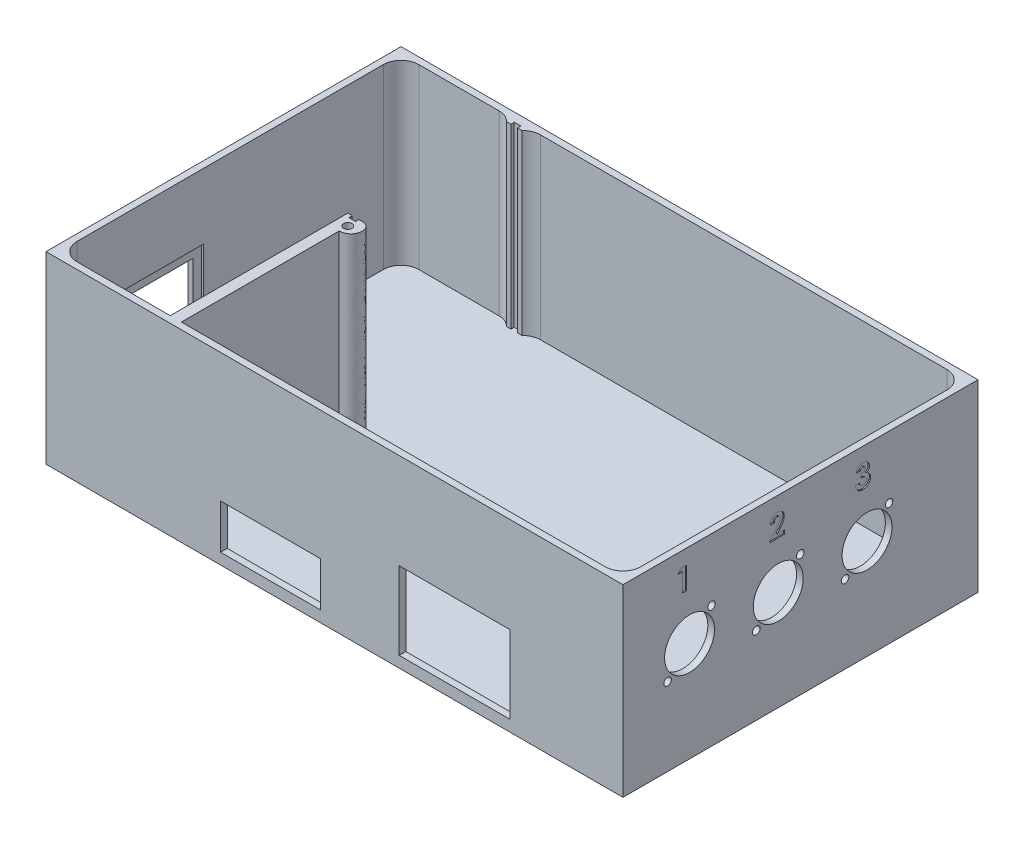
SolidWorks part; units mm, degrees
ref_plane "Ebene vorne" through (0, 0, 0) normal (0, 0, 1) x (1, 0, 0)
ref_plane "Ebene oben" through (0, 0, 0) normal (0, 1, 0) x (1, 0, 0)
ref_plane "Ebene rechts" through (0, 0, 0) normal (1, 0, 0) x (0, 0, -1)
sketch "Sketch1" plane through (0, 0, 0) normal (0, 1, 0) x (1, 0, 0)
  line L1 (-130, -80) -> (130, -80)
  line L2 (-130, -80) -> (-130, 80)
  line L3 (-130, 80) -> (130, 80)
  line L4 (130, -80) -> (130, 80)
  line L5 (-130, -80) -> (130, 80) construction
  line L6 (-130, 80) -> (130, -80) construction
  point P0 (0, 0)
  dimension "D1" = 260
  dimension "D2" = 160
extrude "Boss-Extrude1" add sketch "Sketch1" against normal blind 3
sketch "Sketch2" plane through (0, 0, 0) normal (0, 1, 0) x (1, 0, 0)
  line L4 (130, -80) -> (130, 80)
  line L5 (130, 80) -> (-130, 80)
  line L6 (-130, 80) -> (-130, -80)
  line L7 (-130, -80) -> (130, -80)
  line L8 (130, -80) -> (130, 80)
  line L9 (130, 80) -> (-130, 80)
  line L10 (-130, 80) -> (-130, -80)
  line L11 (-130, -80) -> (130, -80)
  dimension "D1" = 0
extrude "Extrude-Thin2" add sketch "Sketch2" along normal blind 80 thin thin type one direction reverse wall 3
fillet "Fillet1" radius 8 4 edges at (127, 40, 77) (127, 40, -77) (-127, 40, 77) (-127, 40, -77)
sketch "Sketch3" plane through (0, 0, 0) normal (0, 1, 0) x (1, 0, 0)
  line L0 (-119, -77) -> (119, -77) construction
  line L1 (-77, -77) -> (-72, -77)
  line L2 (-77, -77) -> (-77, 3)
  line L4 (-72, -77) -> (-72, -5.9012)
  line L5 (-127, 69) -> (-127, -69) construction
  line L8 (-77, 3) -> (-75, 3)
  line L9 (-75, 3) -> (-75, 1.5)
  line L10 (-75, 1.5) -> (-72, 1.5)
  line L11 (-72, 1.5) -> (-72, 3)
  line L12 (-72, 3) -> (-70, 3)
  spline S0 degree 3 poles (-72, -5.9012) (-65.4058, -5.4857) (-65.3292, 2.681) (-70, 3) knots 0 0 0 0 1 1 1 1
  dimension "D1" = 50
  dimension "D2" = 2
  dimension "D3" = 80
  dimension "D5" = 3
  dimension "D6" = 2
  dimension "D9" = 5
  dimension "D10" = 1.5
extrude "Boss-Extrude2" add sketch "Sketch3" along normal up to surface (80 mm away) up to face at (0, 80, 0)
sketch "Sketch4" plane through (0, 0, 0) normal (0, 1, 0) x (1, 0, 0)
  line L0 (-73.5, 1.5) -> (-73.5, 77) construction
  line L1 (-73.5, 39.25) -> (-68.4781, 39.25) construction
  line L2 (-70, 77) -> (-70, 74.5)
  line L3 (-70, 74.5) -> (-72, 74.5)
  line L4 (-72, 74.5) -> (-72, 76)
  line L5 (-72, 76) -> (-75, 76)
  line L6 (-75, 76) -> (-75, 74.5)
  line L7 (-75, 74.5) -> (-77, 74.5)
  line L8 (-77, 74.5) -> (-77, 77)
  line L9 (-70, 77) -> (-77, 77)
  line L10 (-72, 1.5) -> (-75, 1.5) construction
  line L11 (119, 77) -> (-119, 77) construction
  point P12 (-73.5, 76)
  dimension "D1" = 1.5
  dimension "D2" = 2.5
  dimension "D3" = 2
extrude "Boss-Extrude3" add sketch "Sketch4" along normal up to surface (80 mm away) up to face at (0, 80, 0)
fillet "Fillet2" radius 8 2 edges at (-77, 40, -77) (-70, 40, -77)
sketch "Sketch5" plane through (-130, 0, 0) normal (-1, 0, 0) x (0, 0, 1)
  line L0 (-80, -3) -> (80, -3) construction
  line L1 (63.95, 17.55) -> (16.05, 17.55)
  line L2 (63.95, 17.55) -> (63.95, 46.45)
  line L3 (63.95, 46.45) -> (16.05, 46.45)
  line L4 (16.05, 17.55) -> (16.05, 46.45)
  line L5 (63.95, 17.55) -> (16.05, 46.45) construction
  line L6 (63.95, 46.45) -> (16.05, 17.55) construction
  line L7 (80, -3) -> (80, 80) construction
  point P0 (40, 32)
  dimension "D1" = 28.9
  dimension "D2" = 47.9
  dimension "D3" = 35
  dimension "D4" = 40
extrude "Cut-Extrude1" cut sketch "Sketch5" against normal up to next
sketch "Sketch6" plane through (-127, 0, 0) normal (-1, 0, 0) x (0, 0, 1)
  line L0 (12.05, 13.55) -> (67.95, 13.55)
  line L1 (67.95, 13.55) -> (67.95, 50.45)
  line L2 (67.95, 50.45) -> (12.05, 50.45)
  line L3 (12.05, 50.45) -> (12.05, 13.55)
  line L4 (16.05, 17.55) -> (63.95, 17.55)
  line L5 (16.05, 46.45) -> (16.05, 17.55)
  line L6 (63.95, 46.45) -> (16.05, 46.45)
  line L7 (63.95, 17.55) -> (63.95, 46.45)
  line L8 (16.05, 17.55) -> (63.95, 17.55) construction
  line L9 (16.05, 46.45) -> (16.05, 17.55) construction
  line L10 (63.95, 46.45) -> (16.05, 46.45) construction
  line L11 (63.95, 17.55) -> (63.95, 46.45) construction
  dimension "D1" = 0
  dimension "D2" = 4
extrude "Cut-Extrude2" cut sketch "Sketch6" along normal blind 0.8
sketch "Sketch8" plane through (130, 0, 0) normal (1, 0, 0) x (0, 0, -1)
  line L0 (-61.25, 42) -> (-38.75, 42) construction
  line L1 (-50, 53.25) -> (-50, 30.75) construction
  line L2 (-40.1, 51.9) -> (-59.9, 32.1) construction
  line L3 (-80, -3) -> (-80, 80) construction
  line L4 (-80, -3) -> (80, -3) construction
  line L5 (-21.25, 42) -> (1.25, 42) construction
  line L6 (-10, 53.25) -> (-10, 30.75) construction
  line L7 (-0.1, 51.9) -> (-19.9, 32.1) construction
  line L8 (18.75, 42) -> (41.25, 42) construction
  line L9 (30, 53.25) -> (30, 30.75) construction
  line L10 (39.9, 51.9) -> (20.1, 32.1) construction
  circle A0 centre (-50, 42) radius 11.25
  circle A1 centre (-40.1, 51.9) radius 1.7
  circle A2 centre (-59.9, 32.1) radius 1.7
  circle A3 centre (-10, 42) radius 11.25
  circle A4 centre (-0.1, 51.9) radius 1.7
  circle A5 centre (-19.9, 32.1) radius 1.7
  circle A6 centre (30, 42) radius 11.25
  circle A7 centre (39.9, 51.9) radius 1.7
  circle A8 centre (20.1, 32.1) radius 1.7
  dimension "D1" = 3.4
  dimension "D2" = 22.5
  dimension "D3" = 19.8
  dimension "D4" = 19.8
  dimension "D5" = 30
  dimension "D6" = 45
  dimension "D7" = 3
extrude "Cut-Extrude3" cut sketch "Sketch8" against normal up to surface (3 mm away) up to face at (127, 40, 0)
sketch "Sketch9" plane through (130, 0, 0) normal (1, 0, 0) x (0, 0, -1)
  line L0 (-67.2385, 63.3073) -> (47.8209, 63.3073) construction
  text T0 "1         2        3   " font "Century Gothic" height 10
  point P3 (0, 0)
  point P4 (0, 0)
  point P5 (0, 0)
  point P6 (0, 0)
  point P7 (0, 0)
extrude "Cut-Extrude4" cut sketch "Sketch9" against normal blind 0.5
sketch "Sketch10" plane through (0, 80, 0) normal (0, 1, 0) x (1, 0, 0)
  line L0 (-130, 80) -> (-130, -80) construction
  line L1 (-130, -80) -> (130, -80) construction
  circle A0 centre (-72, -2) radius 1.9
  point P2 (0, 0)
  dimension "D1" = 3.8
  dimension "D2" = 58
  dimension "D3" = 78
extrude "Cut-Extrude5" cut sketch "Sketch10" against normal blind 15
sketch "Sketch11" plane through (0, 0, 80) normal (0, 0, 1) x (1, 0, 0)
  line L1 (-51.3186, 2) -> (-6.3186, 2)
  line L2 (-51.3186, 2) -> (-51.3186, 22)
  line L3 (-51.3186, 22) -> (-6.3186, 22)
  line L4 (-6.3186, 2) -> (-6.3186, 22)
  line L5 (-130, -3) -> (130, -3) construction
  line L6 (29.1814, 2) -> (79.1814, 2)
  line L7 (29.1814, 2) -> (29.1814, 37)
  line L8 (29.1814, 37) -> (79.1814, 37)
  line L9 (79.1814, 2) -> (79.1814, 37)
  line L17 (-70.3186, 0) -> (95.6814, 0)
  line L18 (-70.3186, 1.5) -> (-70.3186, 0)
  line L19 (-56.3186, 1.5) -> (-70.3186, 1.5)
  line L20 (-56.3186, 41) -> (-56.3186, 1.5)
  line L21 (81.6814, 41) -> (-56.3186, 41)
  line L22 (81.6814, 1.5) -> (81.6814, 41)
  line L23 (95.6814, 1.5) -> (81.6814, 1.5)
  line L24 (95.6814, 0) -> (95.6814, 1.5)
  line L25 (-70.3186, 0) -> (95.6814, 0) construction
  line L26 (-70.3186, 1.5) -> (-70.3186, 0) construction
  line L27 (-56.3186, 1.5) -> (-70.3186, 1.5) construction
  line L28 (-56.3186, 41) -> (-56.3186, 1.5) construction
  line L29 (81.6814, 41) -> (-56.3186, 41) construction
  line L30 (81.6814, 1.5) -> (81.6814, 41) construction
  line L31 (95.6814, 1.5) -> (81.6814, 1.5) construction
  line L32 (95.6814, 0) -> (95.6814, 1.5) construction
  dimension "D1" = 45
  dimension "D2" = 20
  dimension "D3" = 35
  dimension "D4" = 50
  dimension "D6" = 5
  dimension "D7" = 5
  dimension "D8" = 5
  dimension "D9" = 5
  dimension "D5" = 0
extrude "Cut-Extrude6" cut sketch "Sketch11" against normal up to surface (3 mm away) up to face at (23.5, 40, 77)
